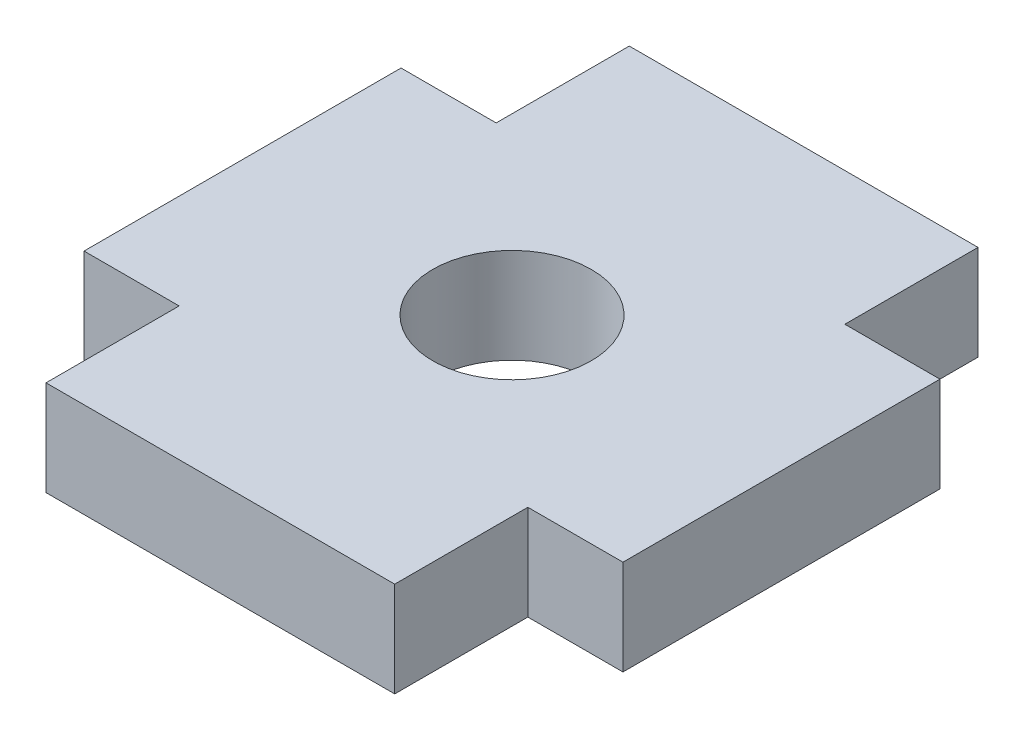
SolidWorks part; units mm, degrees
material "MDF"
ref_plane "Plano frontal" through (0, 0, 0) normal (0, 0, 1) x (1, 0, 0)
ref_plane "Plano superior" through (0, 0, 0) normal (0, 1, 0) x (1, 0, 0)
ref_plane "Plano direito" through (0, 0, 0) normal (1, 0, 0) x (0, 0, -1)
ref_plane "Plano1" through (0, 10, 0) normal (0, -1, 0) x (1, 0, 0)
sketch "Esboço1" plane through (0, 10, 0) normal (0, -1, 0) x (1, 0, 0)
  line L0 (-65.5, -9.1999) -> (-65.5, -5)
  line L1 (-65.5, -5) -> (-62.5, -5)
  line L2 (-62.5, -5) -> (-62.5, 5)
  line L3 (-62.5, 5) -> (-65.5, 5)
  line L4 (-65.5, 5) -> (-65.5, 9.1999)
  line L5 (-65.5, 9.1999) -> (-76.5, 9.1999)
  line L6 (-76.5, 9.1999) -> (-76.5, 5)
  line L7 (-76.5, 5) -> (-79.5, 5)
  line L8 (-79.5, 5) -> (-79.5, -5)
  line L9 (-79.5, -5) -> (-76.5, -5)
  line L10 (-76.5, -5) -> (-76.5, -9.1999)
  line L11 (-76.5, -9.1999) -> (-65.5, -9.1999)
  line L12 (-65.5, 9.1999) -> (-76.5, -9.1999) construction
  line L13 (-65.5, -9.1999) -> (-76.5, 9.1999) construction
  circle A0 centre (-71, 0) radius 2.5
  dimension "D7" = 5
  dimension "D1" = 11
  dimension "D2" = 4.1999
  dimension "D3" = 4.1999
  dimension "D4" = 3
  dimension "D5" = 10
  dimension "D6" = 3
extrude "Ressalto-extrusão1" add sketch "Esboço1" against normal blind 3
